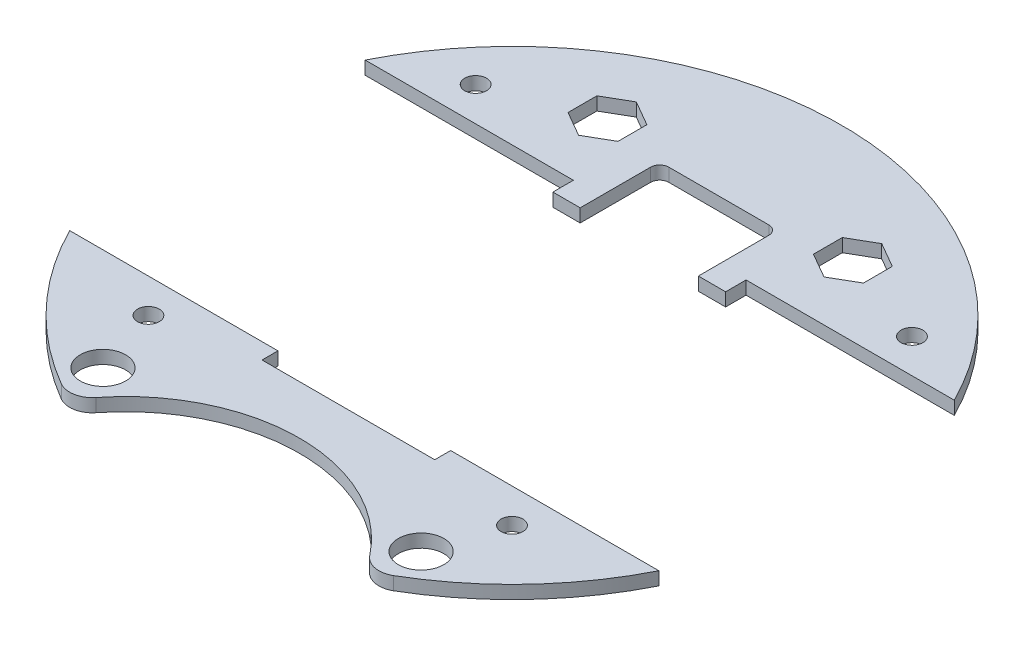
SolidWorks part; units mm, degrees
material "Acrylic (Medium-high impact)"
ref_plane "Front Plane" through (0, 0, 0) normal (0, 0, 1) x (1, 0, 0)
ref_plane "Top Plane" through (0, 0, 0) normal (0, 1, 0) x (1, 0, 0)
ref_plane "Right Plane" through (0, 0, 0) normal (1, 0, 0) x (0, 0, -1)
sketch "Sketch1" plane through (0, 0, 0) normal (0, 1, 0) x (1, 0, 0)
  line L0 (0, -85) -> (-32.4891, -64.8129) construction
  line L1 (0, -85) -> (0, 0) construction
  arc A0 (36.5434, -62.6165) -> (-36.5434, -62.6165) centre (0, 0) ccw
  arc A1 (30.0898, -61.3851) -> (-30.0898, -61.3851) centre (0, -85) ccw
  arc A2 (36.5434, -62.6165) -> (30.0898, -61.3851) centre (34.0231, -58.2982) cw
  arc A3 (-30.0898, -61.3851) -> (-36.5434, -62.6165) centre (-34.0231, -58.2982) cw
  dimension "D1" = 145
  dimension "D2" = 76.5
  dimension "D4" = 5
  dimension "D3" = 85
extrude "Boss-Extrude1" add sketch "Sketch1" along normal blind 2.9
sketch "solenoid placement" plane through (0, 2.9, 0) normal (0, 1, 0) x (1, 0, 0)
  line L4 (-19, -36) -> (19, -36)
  line L5 (-19, 28) -> (-19, -36)
  line L6 (19, 28) -> (-19, 28)
  line L7 (19, -36) -> (19, 28)
  line L8 (-19, -36) -> (19, -36)
  line L9 (-19, 28) -> (-19, -36)
  line L10 (19, 28) -> (-19, 28)
  line L11 (19, -36) -> (19, 28)
  dimension "D1" = 0
extrude "Cut-Extrude1" cut sketch "solenoid placement" against normal through all
sketch "Sketch5" plane through (0, 2.9, 0) normal (0, 1, 0) x (1, 0, 0)
  line L12 (-21.5, 51.1754) -> (-27, 54.3509)
  line L13 (-27, 54.3509) -> (-32.5, 51.1754)
  line L14 (-32.5, 51.1754) -> (-32.5, 44.8246)
  line L15 (-32.5, 44.8246) -> (-27, 41.6491)
  line L16 (-27, 41.6491) -> (-21.5, 44.8246)
  line L17 (-21.5, 44.8246) -> (-21.5, 51.1754)
  line L18 (-21.5, 51.1754) -> (-27, 54.3509)
  line L19 (-27, 54.3509) -> (-32.5, 51.1754)
  line L20 (-32.5, 51.1754) -> (-32.5, 44.8246)
  line L21 (-32.5, 44.8246) -> (-27, 41.6491)
  line L22 (-27, 41.6491) -> (-21.5, 44.8246)
  line L23 (-21.5, 44.8246) -> (-21.5, 51.1754)
  line L24 (21.5, 51.1754) -> (21.5, 44.8246)
  line L25 (21.5, 44.8246) -> (27, 41.6491)
  line L26 (27, 41.6491) -> (32.5, 44.8246)
  line L27 (32.5, 44.8246) -> (32.5, 51.1754)
  line L28 (32.5, 51.1754) -> (27, 54.3509)
  line L29 (27, 54.3509) -> (21.5, 51.1754)
  line L30 (21.5, 51.1754) -> (21.5, 44.8246)
  line L31 (21.5, 44.8246) -> (27, 41.6491)
  line L32 (27, 41.6491) -> (32.5, 44.8246)
  line L33 (32.5, 44.8246) -> (32.5, 51.1754)
  line L34 (32.5, 51.1754) -> (27, 54.3509)
  line L35 (27, 54.3509) -> (21.5, 51.1754)
  dimension "D1" = 0
  dimension "D2" = 0
extrude "Cut-Extrude5" cut sketch "Sketch5" against normal through all
sketch "Sketch6" plane through (0, 2.9, 0) normal (0, 1, 0) x (1, 0, 0)
  circle A1 centre (40, -40) radius 2.4
  circle A2 centre (40, -40) radius 2.4
  circle A3 centre (-40, -40) radius 2.4
  circle A4 centre (-40, -40) radius 2.4
  circle A5 centre (48, 40) radius 2.4
  circle A6 centre (48, 40) radius 2.4
  circle A7 centre (-48, 40) radius 2.4
  circle A8 centre (-48, 40) radius 2.4
  dimension "D1" = 0
  dimension "D2" = 0
  dimension "D3" = 0
  dimension "D4" = 0
extrude "Cut-Extrude6" cut sketch "Sketch6" against normal through all
sketch "Sketch3" plane through (0, 2.9, 0) normal (0, 1, 0) x (1, 0, 0)
  line L0 (-19, 28) -> (-19, 32.5)
  line L1 (72.5, -32.5) -> (-72.5, -32.5)
  line L2 (72.5, -32.5) -> (72.5, 32.5)
  line L3 (72.5, 32.5) -> (19, 32.5)
  line L4 (-72.5, -32.5) -> (-72.5, 32.5)
  line L5 (72.5, -32.5) -> (-72.5, 32.5) construction
  line L6 (72.5, 32.5) -> (-72.5, -32.5) construction
  line L7 (-19, 28) -> (19, 28)
  line L8 (19, 28) -> (19, 32.5)
  line L9 (-19, 32.5) -> (-72.5, 32.5)
  arc A0 (36.5434, -62.6165) -> (-36.5434, -62.6165) centre (0, 0) ccw construction
  point P0 (0, 0)
  dimension "D1" = 65
extrude "Cut-Extrude3" cut sketch "Sketch3" against normal through all
sketch "Sketch7" plane through (0, 2.9, 0) normal (0, 1, 0) x (1, 0, 0)
  line L8 (13, 28) -> (13, 43.5)
  line L9 (-13, 28) -> (13, 28)
  line L10 (-13, 43.5) -> (-13, 28)
  line L11 (11, 45.5) -> (-11, 45.5)
  line L20 (13, 28) -> (13, 43.5)
  line L21 (-13, 28) -> (13, 28)
  line L22 (-13, 43.5) -> (-13, 28)
  line L23 (11, 45.5) -> (-11, 45.5)
  arc A4 (-11, 45.5) -> (-13, 43.5) centre (-11, 43.5) ccw
  arc A5 (13, 43.5) -> (11, 45.5) centre (11, 43.5) ccw
  arc A10 (-11, 45.5) -> (-13, 43.5) centre (-11, 43.5) ccw
  arc A11 (13, 43.5) -> (11, 45.5) centre (11, 43.5) ccw
  dimension "D1" = 0
extrude "Cut-Extrude7" cut sketch "Sketch7" against normal through all
sketch "Sketch8" plane through (0, 2.9, 0) normal (0, -1, 0) x (1, 0, 0)
  circle A1 centre (35, 55) radius 5
  circle A2 centre (35, 55) radius 5
  circle A3 centre (-35, 55) radius 5
  circle A4 centre (-35, 55) radius 5
  dimension "D1" = 0
  dimension "D2" = 0
extrude "Cut-Extrude9" cut sketch "Sketch8" along normal through all
equation "\"smallPulleyTeeth\"= 15"
equation "\"largePulleyTeeth\"= 30"
equation "\"eighthThick\"= 2.9mm"
equation "\"sixteenthThick\" = 1.7mm"
equation "\"quarterThick\"=6.0mm"
equation "\"OD\" = 145mm"
equation "\"puckAngle\" = 60.5deg"
equation "\"D1@Sketch1\"=\"OD\""
equation "\"puckDiam\" = 76.5mm"
equation "\"D2@Sketch1\"=\"puckDiam\""
equation "\"D1@Boss-Extrude1\"=\"eighthThick\""
equation "\"axlePress\" = 5.9mm"
equation "\"press\" = 0.2mm"
equation "\"wheelClear\" = 0.3mm"
equation "\"10-32clear\" = 4.8mm"
equation "\"6-32clear\" = 3.3mm"
equation "\"8-32clear\" = 4.0mm"
equation "\"wheelHeight\" = 22mm"
equation "\"wheelWell\" = 65mm"
equation "\"D1@Sketch3\"=\"wheelWell\""
equation "\"puckDist\" = 85mm"
equation "\"scoopFillet\" = 5mm"
equation "\"4-40clear\" = 3.0mm"
equation "\"D3@Sketch1\"=\"puckDist\""
equation "\"D4@Sketch1\"=\"scoopFillet\""
